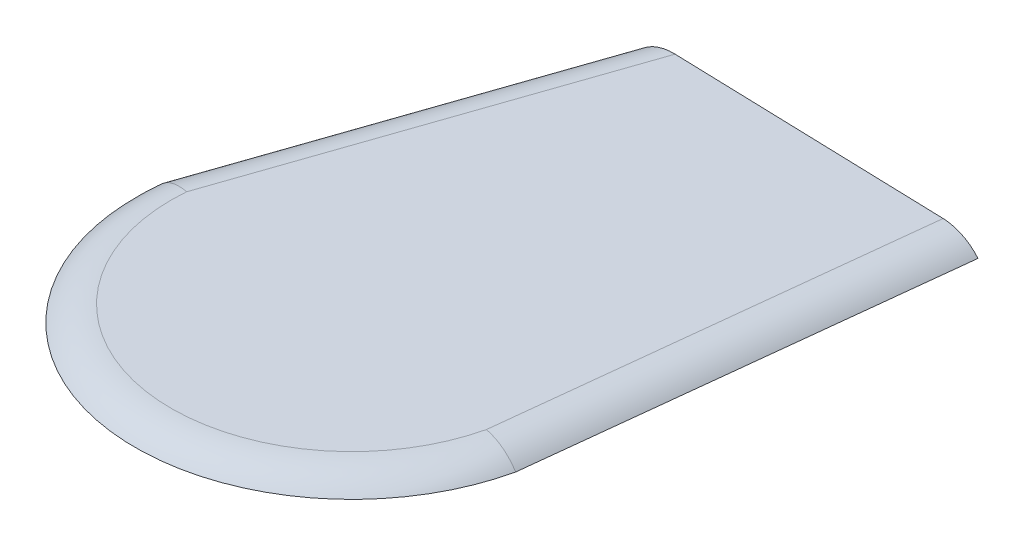
SolidWorks part; units mm, degrees
ref_plane "Front Plane" through (0, 0, 0) normal (0, 0, 1) x (1, 0, 0)
ref_plane "Top Plane" through (0, 0, 0) normal (0, 1, 0) x (1, 0, 0)
ref_plane "Right Plane" through (0, 0, 0) normal (1, 0, 0) x (0, 0, -1)
sketch "Sketch1" plane through (0, 0, 0) normal (0, 1, 0) x (1, 0, 0)
  line L0 (0.5967, 22.5443) -> (-43.0392, 23.8579)
  line L1 (-43.0392, 23.8579) -> (-58.3617, -20.6716)
  line L2 (-5.1614, -29.3679) -> (-3.6085, -15.3679)
  line L3 (-3.6085, -15.3679) -> (-16.7288, -12.421)
  line L4 (-16.7288, -12.421) -> (-21.8267, -35.1183)
  line L5 (-21.8267, -35.1183) -> (-45.2433, -29.8588)
  line L6 (-45.2433, -29.8588) -> (-38.6114, -0.3317)
  line L7 (-38.6114, -0.3317) -> (-2.8321, -8.3679)
  line L8 (-2.8321, -8.3679) -> (0.5967, 22.5443)
  line L9 (0.5967, 22.5443) -> (-5.1614, -29.3679)
  arc A0 (-58.3617, -20.6716) -> (-5.1614, -29.3679) centre (-31.5051, -23.451) ccw
extrude "Boss-Extrude1" add sketch "Sketch1" along normal blind 2 contours L1 A0 L2 L3 L4 L5 L6 L7 L8 L0 | L9 L7 L6 L5 L4 L3 region at (-2.0614, 0, -7.1929) region at (-27.9137, 0, 16.9141)
fillet "Fillet1" radius 6 3 edges at (-50.7004, 2, -1.5931) (-35.8608, 2, 50.0974) (-2.2824, 2, 3.4118)
